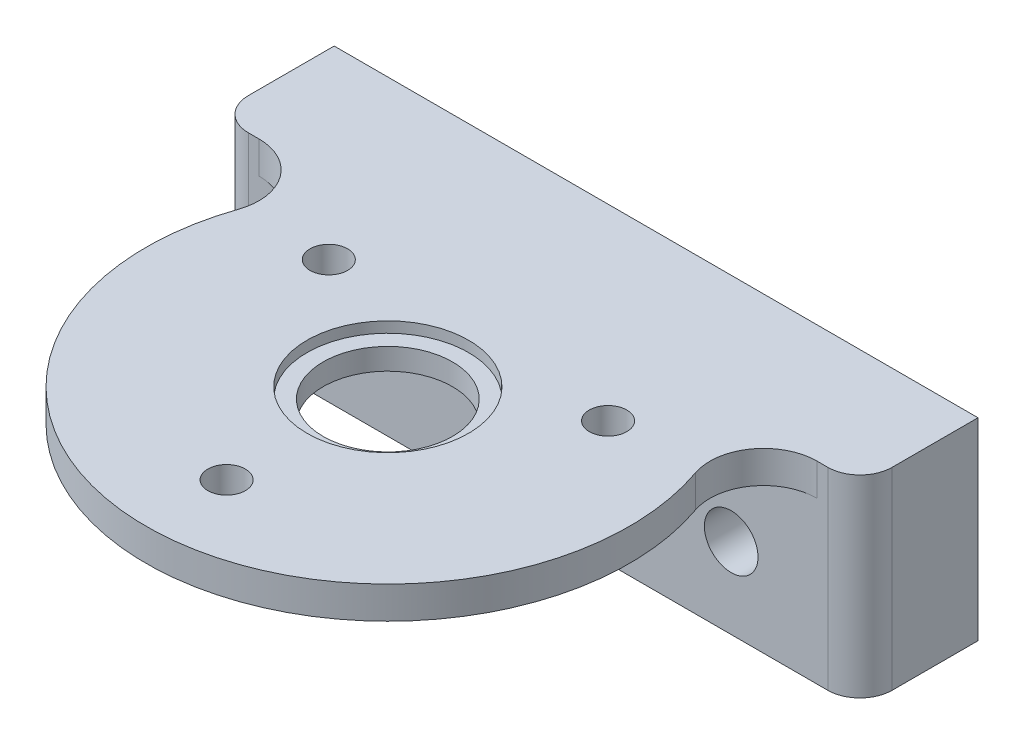
SolidWorks part; units mm, degrees
ref_plane "Front Plane" through (0, 0, 0) normal (0, 0, 1) x (1, 0, 0)
ref_plane "Top Plane" through (0, 0, 0) normal (0, 1, 0) x (1, 0, 0)
ref_plane "Right Plane" through (0, 0, 0) normal (1, 0, 0) x (0, 0, -1)
sketch "Sketch1" plane through (0, 0, 0) normal (0, 1, 0) x (1, 0, 0)
  circle A0 centre (0, 0) radius 7.525
  circle A1 centre (0, 0) radius 6.025
  circle A2 centre (0, 0) radius 22.525
  dimension "D1" = 15.05
  dimension "D2" = 1.5
  dimension "D3" = 15
extrude "Boss-Extrude1" add sketch "Sketch1" along normal blind 2 contours A0 A1 region at (-7.3122, 0, 0)
extrude "Boss-Extrude3" add sketch "Sketch1<5>" along normal offset from surface (3 mm away) 1 contours A2 A0 region at (-21.8879, 0, 0) up to face at (0, 2, 6.025) offset beyond the face yes
sketch "Sketch1<5>" plane through (0, 0, 0) normal (0, 1, 0) x (1, 0, 0) same geometry as "Sketch1"
sketch "Sketch2" plane through (0, 3, 0) normal (0, 1, 0) x (1, 0, 0)
  line L0 (0, -7.525) -> (0, -22.525) construction
  circle A0 centre (0, 0) radius 7.525 construction
  circle A1 centre (0, 0) radius 22.525 construction
  circle A2 centre (0, -15.025) radius 1.75
  dimension "D1" = 3.5
extrude "Cut-Extrude1" cut sketch "Sketch2" against normal blind 4.5
pattern_circular "CirPattern1" count 3 over 360 about axis through (0, 2, 0) along (0, -1, 0) of "Cut-Extrude1"
sketch "Sketch9" plane through (0, 0, 0) normal (0, -1, 0) x (1, 0, 0)
  line L2 (-30, -25) -> (30, -25)
  line L4 (-30, -14) -> (30, -14)
  line L5 (-30, -25) -> (-30, -14)
  line L6 (30, -25) -> (30, -14)
  line L7 (0, 0) -> (0, -25) construction
  line L8 (0, -25) -> (-30, -25) construction
  point P7 (0, -14)
  dimension "D1" = 14
  dimension "D2" = 11
  dimension "D4" = 30
extrude "Boss-Extrude7" add sketch "Sketch9" along normal blind 15 and the other way up to surface (3 mm away) other way up to face at (-14.5276, 3, -8.3875)
sketch "Sketch10" plane through (0, 0, -14) normal (0, 0, 1) x (1, 0, 0)
  line L0 (0, 0) -> (0, -15) construction
  line L3 (-18, -7.5) -> (0, -7.5) construction
  line L5 (30, -15) -> (-30, -15) construction
  line L6 (-17.6458, 0) -> (17.6458, 0) construction
  circle A0 centre (-18, -7.5) radius 2.5
  circle A2 centre (18, -7.5) radius 2.5
  point P11 (0, -15)
  point P15 (0, 0)
  dimension "D2" = 5
  dimension "D1" = 18
extrude "Cut-Extrude3" cut sketch "Sketch10" against normal up to next
fillet "Fillet4" radius 3 2 edges at (-30, -6, -14) (30, -6, -14)
fillet "Fillet5" radius 5 2 edges at (17.6458, 1.5, -14) (-17.6458, 1.5, -14)
